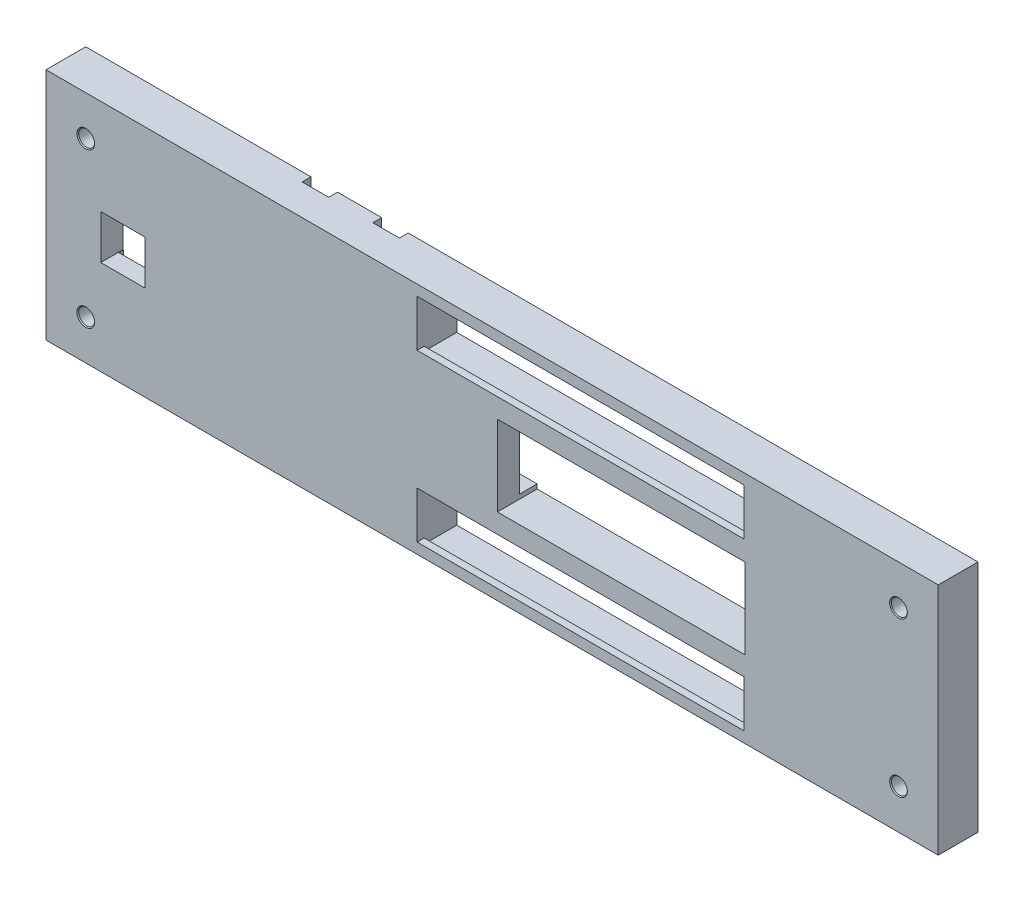
SolidWorks part; units mm, degrees
ref_plane "前视基准面" through (0, 0, 0) normal (0, 0, 1) x (1, 0, 0)
ref_plane "上视基准面" through (0, 0, 0) normal (0, 1, 0) x (1, 0, 0)
ref_plane "右视基准面" through (0, 0, 0) normal (1, 0, 0) x (0, 0, -1)
other "Configuration Table"
sketch "草图1" plane through (0, 0, 0) normal (0, 0, 1) x (1, 0, 0)
  line L1 (0, 0) -> (101, 0)
  line L2 (0, 0) -> (0, 26.5)
  line L3 (0, 26.5) -> (101, 26.5)
  line L4 (101, 0) -> (101, 26.5)
  dimension "D1" = 101
  dimension "D2" = 26.5
extrude "凸台-拉伸1" add sketch "草图1" along normal blind 2.5
sketch "草图7" plane through (0, 0, 0) normal (0, 0, 1) x (1, 0, 0)
  line L0 (0, 26.5) -> (4, 22.5)
  line L1 (0, 26.5) -> (4, 26.5)
  line L2 (0, 26.5) -> (0, 22.5)
  line L3 (0, 22.5) -> (4, 22.5)
  line L4 (4, 26.5) -> (4, 22.5)
  line L5 (0, 0) -> (4, 0)
  line L6 (0, 0) -> (0, 4)
  line L7 (0, 4) -> (4, 4)
  line L8 (4, 0) -> (4, 4)
  line L9 (101, 26.5) -> (97, 26.5)
  line L10 (101, 26.5) -> (101, 22.5)
  line L11 (101, 22.5) -> (97, 22.5)
  line L12 (97, 26.5) -> (97, 22.5)
  line L13 (101, 0) -> (97, 0)
  line L14 (101, 0) -> (101, 4)
  line L15 (101, 4) -> (97, 4)
  line L16 (97, 0) -> (97, 4)
  line L18 (97, 22.5) -> (101, 26.5)
  line L19 (97, 4) -> (101, 0)
  circle A0 centre (2, 24.5) radius 0.5974
  circle A1 centre (1.9156, 1.8995) radius 0.3791
  circle A2 centre (99, 24.5) radius 0.8607
  circle A3 centre (99, 2) radius 0.7914
  point P20 (97, 2)
  point P25 (2, 24.5)
  point P32 (4, 26.5)
  point P34 (4, 26.5)
  point P36 (4, 26.5)
  point P41 (1.9156, 1.8995)
  point P43 (1.9156, 1.8995)
  point P45 (1.9156, 1.8995)
  point P47 (1.9156, 1.8995)
  dimension "D1" = 4
  dimension "D2" = 4
  dimension "D3" = 4
  dimension "D4" = 4
  dimension "D5" = 4
  dimension "D6" = 4
  dimension "D7" = 4
  dimension "D8" = 2
sketch "草图10" plane through (0, 0, 2.5) normal (0, 0, 1) x (1, 0, 0)
  line L0 (101, 26.5) -> (0, 26.5) construction
  line L1 (42, 26.5) -> (79, 26.5)
  line L2 (42, 26.5) -> (42, 19.5)
  line L3 (42, 19.5) -> (79, 19.5)
  line L4 (79, 26.5) -> (79, 19.5)
  line L5 (0, 0) -> (101, 0) construction
  line L6 (42, 0) -> (79, 0)
  line L7 (42, 0) -> (42, 7)
  line L8 (42, 7) -> (79, 7)
  line L9 (79, 0) -> (79, 7)
  line L10 (101, 0) -> (101, 26.5) construction
  dimension "D1" = 22
  dimension "D2" = 22
  dimension "D3" = 37
  dimension "D4" = 37
  dimension "D5" = 7
  dimension "D6" = 7
extrude "切除-拉伸1" cut sketch "草图10" against normal blind 2.5
sketch "草图11" plane through (0, 0, 0) normal (0, 0, -1) x (-1, 0, 0)
  line L12 (-42, 26.5) -> (-42, 19.5)
  line L13 (-42, 19.5) -> (-79, 19.5)
  line L14 (-79, 19.5) -> (-79, 26.5)
  line L15 (-79, 26.5) -> (-101, 26.5)
  line L16 (-101, 26.5) -> (-101, 0)
  line L17 (-101, 0) -> (-79, 0)
  line L18 (-79, 0) -> (-79, 7)
  line L19 (-79, 7) -> (-42, 7)
  line L20 (-42, 7) -> (-42, 0)
  line L21 (-42, 0) -> (0, 0)
  line L22 (0, 0) -> (0, 26.5)
  line L23 (0, 26.5) -> (-42, 26.5)
  line L24 (-42, 26.5) -> (-42, 19.5)
  line L25 (-42, 19.5) -> (-79, 19.5)
  line L26 (-79, 19.5) -> (-79, 26.5)
  line L27 (-79, 26.5) -> (-101, 26.5)
  line L28 (-101, 26.5) -> (-101, 0)
  line L29 (-101, 0) -> (-79, 0)
  line L30 (-79, 0) -> (-79, 7)
  line L31 (-79, 7) -> (-42, 7)
  line L32 (-42, 7) -> (-42, 0)
  line L33 (-42, 0) -> (0, 0)
  line L34 (0, 0) -> (0, 26.5)
  line L35 (0, 26.5) -> (-42, 26.5)
  line L36 (-39.8, 24.3) -> (-39.8, 17.3)
  line L37 (-39.8, 17.3) -> (-81.2, 17.3)
  line L38 (-81.2, 17.3) -> (-81.2, 24.3)
  line L39 (-81.2, 24.3) -> (-98.8, 24.3)
  line L40 (-98.8, 24.3) -> (-98.8, 2.2)
  line L41 (-98.8, 2.2) -> (-81.2, 2.2)
  line L42 (-81.2, 2.2) -> (-81.2, 9.2)
  line L43 (-81.2, 9.2) -> (-39.8, 9.2)
  line L44 (-39.8, 9.2) -> (-39.8, 2.2)
  line L45 (-39.8, 2.2) -> (-2.2, 2.2)
  line L46 (-2.2, 2.2) -> (-2.2, 24.3)
  line L47 (-2.2, 24.3) -> (-39.8, 24.3)
  dimension "D1" = 0
  dimension "D3" = 2.2
extrude "凸台-拉伸2" add sketch "草图11" along normal blind 2
sketch "草图13" plane through (0, 0, 2.5) normal (0, 0, -1) x (-1, 0, 0)
  line L1 (-6.8, 6.8) -> (-2.2, 2.2)
  line L2 (-98.8, 24.3) -> (-94.2, 24.3)
  line L3 (-98.8, 24.3) -> (-98.8, 19.7)
  line L4 (-98.8, 19.7) -> (-94.2, 19.7)
  line L5 (-94.2, 24.3) -> (-94.2, 19.7)
  line L6 (-98.8, 2.2) -> (-94.2, 2.2)
  line L7 (-98.8, 2.2) -> (-98.8, 6.8)
  line L8 (-98.8, 6.8) -> (-94.2, 6.8)
  line L9 (-94.2, 2.2) -> (-94.2, 6.8)
  line L10 (-2.2, 24.3) -> (-6.8, 24.3)
  line L11 (-2.2, 24.3) -> (-2.2, 19.7)
  line L12 (-2.2, 19.7) -> (-6.8, 19.7)
  line L13 (-6.8, 24.3) -> (-6.8, 19.7)
  line L14 (-2.2, 2.2) -> (-6.8, 2.2)
  line L15 (-2.2, 2.2) -> (-2.2, 6.8)
  line L16 (-2.2, 6.8) -> (-6.8, 6.8)
  line L17 (-6.8, 2.2) -> (-6.8, 6.8)
  line L18 (-6.8, 19.7) -> (-2.5224, 23.9776)
  line L21 (-98.8, 24.3) -> (-94.2, 19.7)
  line L22 (-98.8, 2.2) -> (-94.2, 6.8)
  line L23 (-6.8, 24.3) -> (-2.2, 19.7)
  line L25 (-98.8, 24.3) -> (-98.8, 2.2) construction
  line L26 (-81.2, 24.3) -> (-98.8, 24.3) construction
  line L27 (-98.8, 2.2) -> (-81.2, 2.2) construction
  line L28 (-39.8, 2.2) -> (-2.2, 2.2) construction
  line L29 (-2.2, 2.2) -> (-2.2, 24.3) construction
  line L32 (-2.2, 24.3) -> (-39.8, 24.3) construction
  point P26 (-96.5, 22)
  point P28 (-96.5, 4.5)
  point P30 (-4.5, 22)
  point P32 (-4.5, 4.5)
  dimension "D1" = 4.6
  dimension "D2" = 4.6
  dimension "D3" = 4.6
  dimension "D4" = 4.6
  dimension "D5" = 4.6
  dimension "D6" = 4.6
  dimension "D7" = 4.6
  dimension "D8" = 4.6
  dimension "D9" = 0
hole_wizard "M6 开槽半沉头螺钉的锥形沉头孔4" positions "草图13" profile "草图16" countersink size "M6" standard "GB" end condition through all
sketch "草图16" plane through (4.5, 4.5, 2.5) normal (1, 0, 0) x (0, -1, 0)
  line L0 (0, 0) -> (0, 4.5)
  line L1 (0, 4.5) -> (0.9, 4.5)
  line L2 (0.9, 4.5) -> (0.9, 0.1)
  line L3 (0.9, 0.1) -> (1, 0)
  line L5 (1, 0) -> (0, 0)
  line L6 (-0.9, 0.1) -> (-1, 0) construction
  line L11 (0, -6.35) -> (0, 107.95) construction
  dimension "通孔孔直径" = 1.8
  dimension "通孔孔深度" = 4.5
  dimension "近端锥形沉头孔直径" = 2
  dimension "近端锥形沉头孔角度" = 90
sketch "草图17" plane through (0, 0, 0) normal (0, 0, -1) x (-1, 0, 0)
  line L12 (-94.8, 24.3) -> (-94.8, 20.3)
  line L20 (-94.8, 24.3) -> (-98.8, 24.3)
  line L22 (-98.8, 24.3) -> (-98.8, 20.3)
  line L44 (-94.8, 20.3) -> (-98.8, 20.3)
  line L46 (-94.8, 6.2) -> (-94.8, 2.2)
  line L47 (-2.2, 24.3) -> (-6.2, 24.3)
  line L48 (-2.2, 24.3) -> (-2.2, 20.3)
  line L49 (-2.2, 20.3) -> (-6.2, 20.3)
  line L50 (-6.2, 24.3) -> (-6.2, 20.3)
  line L51 (-94.8, 6.2) -> (-98.8, 6.2)
  line L52 (-98.8, 6.2) -> (-98.8, 2.2)
  line L53 (-94.8, 2.2) -> (-98.8, 2.2)
  line L54 (-2.2, 6.2) -> (-2.2, 2.2)
  line L55 (-2.2, 6.2) -> (-6.2, 6.2)
  line L56 (-6.2, 6.2) -> (-6.2, 2.2)
  line L57 (-2.2, 2.2) -> (-6.2, 2.2)
  circle A0 centre (-4.5, 4.5) radius 0.9 construction
  circle A1 centre (-4.5, 22) radius 0.9 construction
  circle A2 centre (-96.5, 4.5) radius 0.9 construction
  circle A3 centre (-96.5, 22) radius 0.9 construction
  circle A4 centre (-4.5, 4.5) radius 0.9
  circle A5 centre (-4.5, 22) radius 0.9
  circle A6 centre (-96.5, 4.5) radius 0.9
  circle A7 centre (-96.5, 22) radius 0.9
  circle M23 centre (-96.5, 22) radius 0.9
  circle M24 centre (-96.5, 4.5) radius 0.9
  circle M25 centre (-4.5, 22) radius 0.9
  circle M26 centre (-4.5, 4.5) radius 0.9
  line M43 (-2.2, 24.3) -> (-39.8, 24.3)
  line M48 (-98.8, 24.3) -> (-98.8, 2.2)
  line M49 (-98.8, 2.2) -> (-81.2, 2.2)
  line M53 (-39.8, 2.2) -> (-2.2, 2.2)
  line M54 (-2.2, 2.2) -> (-2.2, 24.3)
  dimension "D2" = 2
  dimension "D6" = 4
  dimension "D7" = 4
  dimension "D1" = 2
extrude "凸台-拉伸3" add sketch "草图17" along normal up to surface (2 mm away) contours M53 M54 M26 | M54 M43 M25 | M48 M23 | M48 M49 M24 region at (96.8, 6.1434, 0) region at (94.8566, 22.3, 0) region at (2.2566, 22.3, 0) region at (2.2566, 4.2, 0) up to face at (57.1667, 13.25, -2)
sketch "草图18" plane through (0, 0, 2.5) normal (0, 0, 1) x (1, 0, 0)
  line L0 (42, 19.5) -> (79, 19.5) construction
  line L1 (37, 17.8) -> (79.1, 17.8)
  line L2 (37, 17.8) -> (37, 8.7)
  line L3 (37, 8.7) -> (79.1, 8.7)
  line L4 (79.1, 17.8) -> (79.1, 8.7)
  line L5 (79, 7) -> (42, 7) construction
  line L6 (42, 26.5) -> (42, 19.5) construction
  line L7 (79, 0) -> (79, 7) construction
  line L8 (42, 7) -> (42, 0) construction
  line L9 (32, 19.5) -> (37, 19.5)
  line L10 (32, 19.5) -> (32, 7)
  line L11 (32, 7) -> (37, 7)
  line L12 (37, 19.5) -> (37, 7)
  line L13 (79.1, 19.5) -> (84.1, 19.5)
  line L14 (79.1, 19.5) -> (79.1, 7)
  line L15 (79.1, 7) -> (84.1, 7)
  line L16 (84.1, 19.5) -> (84.1, 7)
  dimension "D1" = 1.7
  dimension "D2" = 1.7
  dimension "D3" = 5
  dimension "D4" = 0.1
  dimension "D5" = 5
  dimension "D6" = 0
  dimension "D7" = 0
  dimension "D8" = 0
  dimension "D9" = 5
  dimension "D10" = 5
  dimension "D11" = 0
  dimension "D12" = 0
extrude "切除-拉伸2" cut sketch "草图18" against normal blind 1 contours L12 L9 L10 L11 L2 | L4 L1 L2 L3 | L16 L13 L14 L4 L15 region at (58.05, 13.25, 2.5) region at (34.5, 13.25, 2.5) region at (81.6, 13.25, 2.5)
sketch "草图20" plane through (0, 0, 1.5) normal (0, 0, 1) x (1, 0, 0)
  line L1 (51.1, 17.8) -> (79.1, 17.8)
  line L3 (51.1, 8.7) -> (79.1, 8.7)
  line L4 (79.1, 17.8) -> (79.1, 8.7)
  line L5 (79.1, 17.8) -> (51.1, 17.8)
  line L6 (79.1, 17.8) -> (79.1, 8.7)
  line L7 (79.1, 8.7) -> (51.1, 8.7)
  line L8 (51.1, 17.8) -> (51.1, 8.7)
  line L12 (37, 17.8) -> (37, 19.5)
  line L13 (37, 19.5) -> (32, 19.5)
  line L14 (32, 19.5) -> (32, 7)
  line L15 (32, 7) -> (37, 7)
  line L16 (37, 7) -> (37, 8.7)
  line L17 (37, 8.7) -> (79.1, 8.7)
  line L22 (79.1, 19.5) -> (79.1, 17.8)
  line L23 (79.1, 17.8) -> (37, 17.8)
  line L29 (51.1, 8.7) -> (79.1, 8.7)
  line L35 (79.1, 17.8) -> (51.1, 17.8)
  line L36 (79.1, 8.7) -> (79.1, 7)
  line L37 (79.1, 7) -> (84.1, 7)
  line L38 (84.1, 7) -> (84.1, 19.5)
  line L39 (84.1, 19.5) -> (79.1, 19.5)
  line M18 (37, 8.7) -> (79.1, 8.7)
  line M24 (79.1, 17.8) -> (37, 17.8)
  dimension "D2" = 28
  dimension "D1" = 0
extrude "切除-拉伸3" cut sketch "草图20" against normal up to next contours L4 M24 M18 region at (65.1, 13.25, 1.5)
sketch "草图22" plane through (79, 0, 0) normal (-1, 0, 0) x (0, 0, 1)
  line L0 (2.5, 0) -> (2.5, 7) construction
  line L1 (-2, 0) -> (2.5, 0)
  line L2 (-2, 0) -> (-2, 0.6)
  line L3 (-2, 0.6) -> (1.7, 0.6)
  line L4 (2.5, 0) -> (2.5, 1.146)
  line L5 (0, 13.25) -> (1.5, 13.25)
  line L7 (2.5, 1.146) -> (2.5, 1.2)
  line L8 (2.5, 1.2) -> (1.7, 1.2)
  line L9 (1.7, 0.6) -> (1.7, 1.2)
  line L10 (2.5, 7) -> (1.7, 7)
  line L11 (2.5, 7) -> (2.5, 6.5)
  line L12 (2.5, 6.5) -> (1.7, 6.5)
  line L13 (1.7, 7) -> (1.7, 6.5)
  line L14 (1.5, 13.25) -> (2.8388, 13.25)
  line L15 (0, 17.3) -> (1.5, 17.8)
  line L16 (1.7, 19.5) -> (1.7, 20)
  line L17 (0, 17.3) -> (0, 9.2)
  line L18 (-2, 8.7) -> (1.5, 8.7)
  line L19 (1.5, 8.7) -> (1.5, 17.8)
  line L20 (1.5, 17.8) -> (-2, 17.8)
  line L22 (-2, 8.7) -> (1.5, 8.7)
  line L24 (1.5, 17.8) -> (-2, 17.8)
  line L25 (2.5, 20) -> (1.7, 20)
  line L26 (2.5, 19.5) -> (2.5, 20)
  line L27 (2.5, 19.5) -> (1.7, 19.5)
  line L28 (1.7, 25.9) -> (1.7, 25.3)
  line L29 (2.5, 25.3) -> (1.7, 25.3)
  line L30 (2.5, 25.354) -> (2.5, 25.3)
  line L31 (2.5, 26.5) -> (2.5, 25.354)
  line L32 (-2, 25.9) -> (1.7, 25.9)
  line L33 (-2, 26.5) -> (-2, 25.9)
  line L34 (-2, 26.5) -> (2.5, 26.5)
  line L43 (-2, 17.8) -> (-2, 17.3)
  line L44 (-2, 17.8) -> (-2, 17.3)
  line L45 (-2, 17.3) -> (0, 17.3)
  line L46 (-2, 17.3) -> (0, 17.3)
  line L47 (0, 9.2) -> (-2, 9.2)
  line L48 (0, 9.2) -> (-2, 9.2)
  line L49 (-2, 9.2) -> (-2, 8.7)
  line L50 (-2, 9.2) -> (-2, 8.7)
  line M15 (2.5, 0) -> (2.5, 7)
  line M16 (2.5, 7) -> (-2, 7)
  line M17 (-2, 7) -> (-2, 0)
  line M18 (-2, 0) -> (2.5, 0)
  dimension "D1" = 0.8
  dimension "D2" = 1.2
  dimension "D3" = 0.6
  dimension "D4" = 0.5
  dimension "D5" = 0
extrude "凸台-拉伸4" add sketch "草图22" along normal up to surface (37 mm away) contours L34 L33 L32 L28 L29 L30 L31 | L27 L26 L25 L16 | L13 L12 M16 M15 | L9 L3 L8 M17 M18 M15 region at (79, 0.3906, 0.5292) region at (79, 6.75, 2.1) region at (79, 19.75, 2.1) region at (79, 26.1094, 0.5292) up to face at (42, 23, 0.25)
sketch "草图23" plane through (0, 0, 1.5) normal (0, 0, 1) x (1, 0, 0)
  line L6 (79.1, 19.5) -> (79.1, 17.8)
  line L7 (79.1, 17.8) -> (79.1, 8.7)
  line L8 (51.1, 8.7) -> (51.1, 17.8)
  line L9 (51.1, 17.8) -> (37, 17.8)
  line L10 (37, 17.8) -> (37, 19.5)
  line L11 (37, 19.5) -> (32, 19.5)
  line L12 (32, 19.5) -> (32, 7)
  line L13 (32, 7) -> (37, 7)
  line L14 (37, 7) -> (37, 8.7)
  line L15 (37, 8.7) -> (51.1, 8.7)
  line L16 (51.1, 8.7) -> (51.1, 17.8)
  line L17 (51.1, 17.8) -> (37, 17.8)
  line L18 (37, 17.8) -> (37, 19.5)
  line L19 (37, 19.5) -> (32, 19.5)
  line L20 (32, 19.5) -> (32, 7)
  line L21 (32, 7) -> (37, 7)
  line L22 (37, 7) -> (37, 8.7)
  line L23 (37, 8.7) -> (51.1, 8.7)
  line L24 (79.1, 8.7) -> (79.1, 7)
  line L25 (79.1, 7) -> (84.1, 7)
  line L26 (84.1, 7) -> (84.1, 19.5)
  line L27 (84.1, 19.5) -> (79.1, 19.5)
  line L28 (79.1, 19.5) -> (79.1, 17.8)
  line L29 (79.1, 17.8) -> (79.1, 8.7)
  line L30 (79.1, 8.7) -> (79.1, 7)
  line L31 (79.1, 7) -> (84.1, 7)
  line L32 (84.1, 7) -> (84.1, 19.5)
  line L33 (84.1, 19.5) -> (79.1, 19.5)
  line M15 (51.1, 8.7) -> (51.1, 17.8)
  line M16 (51.1, 17.8) -> (37, 17.8)
  line M17 (37, 17.8) -> (37, 19.5)
  line M18 (37, 19.5) -> (32, 19.5)
  line M19 (32, 19.5) -> (32, 7)
  line M20 (32, 7) -> (37, 7)
  line M21 (37, 7) -> (37, 8.7)
  line M22 (37, 8.7) -> (51.1, 8.7)
  dimension "D1" = 0
  dimension "D2" = 0
extrude "凸台-拉伸5" add sketch "草图23" along normal up to surface (1 mm away) contours M22 M15 M16 M17 M18 M19 M20 M21 | L32 L33 L28 L29 L30 L31 | L16 L17 L18 L19 L20 L21 L22 L23 region at (81.6, 13.25, 1.5) region at (40.9219, 13.25, 1.5) up to face at (60.5, 3.85, 2.5)
sketch "草图24" plane through (0, 0, 0) normal (0, -1, 0) x (1, 0, 0)
  line L0 (101, -2) -> (0, -2) construction
  line L1 (6.25, -2) -> (16.25, -2)
  line L2 (6.25, -2) -> (6.25, 0.5)
  line L3 (6.25, 0.5) -> (16.25, 0.5)
  line L4 (16.25, -2) -> (16.25, 0.5)
  line L5 (0, 2.5) -> (0, -2) construction
  line L7 (18.25, -2) -> (21.25, -2)
  line L8 (18.25, -2) -> (18.25, -1)
  line L9 (18.25, -1) -> (21.25, -1)
  line L10 (21.25, -2) -> (21.25, -1)
  line L11 (26.25, -2) -> (29.25, -2)
  line L12 (26.25, -2) -> (26.25, -1)
  line L13 (26.25, -1) -> (29.25, -1)
  line L14 (29.25, -2) -> (29.25, -1)
  line L15 (34.25, -2) -> (37.25, -2)
  line L16 (34.25, -2) -> (34.25, -1)
  line L17 (34.25, -1) -> (37.25, -1)
  line L18 (37.25, -2) -> (37.25, -1)
  dimension "D1" = 2.5
  dimension "D2" = 10
  dimension "D3" = 6.25
  dimension "D4" = 2
  dimension "D5" = 3
  dimension "D6" = 1
  dimension "D7" = 5
  dimension "D8" = 3
  dimension "D9" = 1
  dimension "D10" = 1
  dimension "D11" = 3
  dimension "D12" = 5
extrude "切除-拉伸4" cut sketch "草图24" against normal blind 15
chamfer "倒角1" distance 2 angle 45 3 edges at (16.25, 0, -0.75) (11.25, 0, 0.5) (6.25, 0, -0.75)
sketch "草图25" plane through (0, 26.5, 0) normal (0, 1, 0) x (1, 0, 0)
  line L0 (0, 2) -> (101, 2) construction
  line L1 (25.5, 2) -> (28.5, 2)
  line L2 (25.5, 2) -> (25.5, 1)
  line L3 (25.5, 1) -> (28.5, 1)
  line L4 (28.5, 2) -> (28.5, 1)
  line L5 (0, -2.5) -> (0, 2) construction
  line L11 (33.5, 1) -> (36.5, 1)
  line L12 (33.5, 1) -> (33.5, 2)
  line L13 (33.5, 2) -> (36.5, 2)
  line L14 (36.5, 1) -> (36.5, 2)
  dimension "D1" = 25.5
  dimension "D2" = 3
  dimension "D3" = 1
  dimension "D4" = 5
  dimension "D5" = 3
  dimension "D6" = 1
extrude "切除-拉伸5" cut sketch "草图25" against normal up to next
sketch "草图27" plane through (0, 0, 0) normal (0, 0, -1) x (-1, 0, 0)
  line L0 (-2.2, 6.2) -> (-6.2, 6.2) construction
  line L1 (-11.2, 15.7) -> (-6.2, 15.7)
  line L2 (-11.2, 15.7) -> (-11.2, 10.7)
  line L3 (-11.2, 10.7) -> (-6.2, 10.7)
  line L4 (-6.2, 15.7) -> (-6.2, 10.7)
  line L5 (-2.2, 6.2) -> (-2.2, 20.3) construction
  dimension "D1" = 5
  dimension "D2" = 4.5
  dimension "D3" = 4
extrude "切除-拉伸6" cut sketch "草图27" against normal blind 9
sketch "草图28" plane through (0, 0, -2) normal (0, 0, -1) x (-1, 0, 0)
  line L0 (-6.2, 24.3) -> (-39.8, 24.3) construction
  line L1 (-38.8, 24.3) -> (-23.8, 24.3)
  line L2 (-38.8, 24.3) -> (-38.8, 25.3)
  line L3 (-38.8, 25.3) -> (-23.8, 25.3)
  line L4 (-23.8, 24.3) -> (-23.8, 25.3)
  line L5 (-39.8, 24.3) -> (-39.8, 17.3) construction
  line L6 (-16.25, 15) -> (-16.25, 2) construction
  line L7 (-39.8, 2.2) -> (-16.25, 2.2)
  line L8 (-39.8, 2.2) -> (-39.8, 1.2)
  line L9 (-39.8, 1.2) -> (-16.25, 1.2)
  line L10 (-16.25, 2.2) -> (-16.25, 1.2)
  dimension "D1" = 1
  dimension "D2" = 15
  dimension "D3" = 1
  dimension "D4" = 1
  dimension "D5" = 0
extrude "切除-拉伸7" cut sketch "草图28" against normal up to surface (2 mm away) up to face at (18.52, 12.31, 0)
